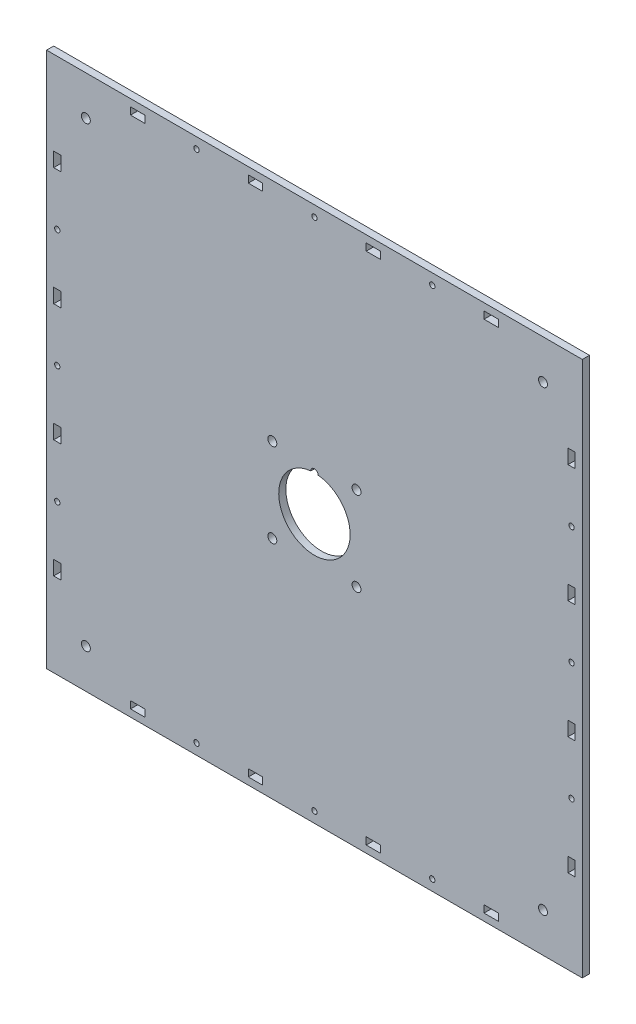
SolidWorks part; units mm, degrees
ref_plane "前视基准面" through (0, 0, 0) normal (0, 0, 1) x (1, 0, 0)
ref_plane "上视基准面" through (0, 0, 0) normal (0, 1, 0) x (1, 0, 0)
ref_plane "右视基准面" through (0, 0, 0) normal (1, 0, 0) x (0, 0, -1)
sketch "草图1" plane through (0, 0, 0) normal (0, 0, 1) x (1, 0, 0)
  line L0 (1.4571, -21.1871) -> (1.4571, -41.1871) construction
  line L2 (1.4571, -21.1871) -> (1.4571, 44.8129) construction
  line L4 (151.4571, -41.1871) -> (151.4571, 108.8129)
  line L5 (151.4571, 108.8129) -> (-148.5429, 108.8129)
  line L6 (-148.5429, 108.8129) -> (-148.5429, -191.1871)
  line L7 (-148.5429, -191.1871) -> (151.4571, -191.1871)
  line L8 (151.4571, -191.1871) -> (151.4571, -41.1871)
  line L9 (-148.5429, -41.1871) -> (-161.9412, -41.1871) construction
  line L10 (1.4571, -191.1871) -> (1.4571, -181.0361) construction
  circle A6 centre (1.4571, -21.1871) radius 241.4173 construction
  circle A9 centre (1.4571, -41.1871) radius 20
  circle A10 centre (25.0271, -17.6171) radius 2.5
  circle A11 centre (25.0271, -64.7571) radius 2.5
  circle A12 centre (-22.1129, -64.7571) radius 2.5
  circle A13 centre (-22.1129, -17.6171) radius 2.5
  dimension "D1" = 40
  dimension "D4" = 5
  dimension "D2" = 300
  dimension "D3" = 300
  dimension "D5" = 23.57
  dimension "D6" = 23.57
  dimension "D7" = 4
extrude "凸台-拉伸1" add sketch "草图1" along normal blind 4
sketch "草图2" plane through (0, 0, 4) normal (0, 0, 1) x (1, 0, 0)
  line L0 (-18.5429, -1.1871) -> (21.4571, -41.1871) construction
  circle A0 centre (1.4571, -21.1871) radius 2
extrude "切除-拉伸1" cut sketch "草图2" against normal blind 4 contours A0
sketch "草图3" plane through (0, 0, 4) normal (0, 0, 1) x (1, 0, 0)
  line L1 (96.4421, -183.1721) -> (104.4721, -183.1721)
  line L13 (1.4571, -191.1871) -> (1.4571, -185.1871) construction
  line L14 (-148.5429, -191.1871) -> (151.4571, -191.1871) construction
  line L15 (1.4571, -185.1871) -> (34.4571, -185.1871) construction
  line L16 (34.4571, -185.1871) -> (67.4571, -185.1871) construction
  line L17 (30.4421, -183.1721) -> (38.4721, -183.1721)
  line L18 (30.4421, -183.1721) -> (30.4421, -187.2021)
  line L19 (30.4421, -187.2021) -> (38.4721, -187.2021)
  line L20 (38.4721, -183.1721) -> (38.4721, -187.2021)
  line L21 (30.4421, -183.1721) -> (38.4721, -187.2021) construction
  line L22 (30.4421, -187.2021) -> (38.4721, -183.1721) construction
  line L23 (67.4571, -185.1871) -> (100.4571, -185.1871) construction
  line L24 (96.4421, -183.1721) -> (96.4421, -187.2021)
  line L25 (96.4421, -187.2021) -> (104.4721, -187.2021)
  line L26 (96.4421, -187.2021) -> (104.4721, -183.1721) construction
  line L27 (104.4721, -187.2021) -> (104.4721, -183.1721)
  line L28 (-35.5579, -183.1721) -> (-35.5579, -187.2021)
  line L29 (-27.5279, -183.1721) -> (-35.5579, -183.1721)
  line L30 (-27.5279, -183.1721) -> (-27.5279, -187.2021)
  line L31 (-27.5279, -187.2021) -> (-35.5579, -187.2021)
  line L32 (-93.5279, -183.1721) -> (-93.5279, -187.2021)
  line L33 (-101.5579, -187.2021) -> (-101.5579, -183.1721)
  line L34 (-93.5279, -183.1721) -> (-101.5579, -183.1721)
  line L35 (-93.5279, -187.2021) -> (-101.5579, -187.2021)
  line L36 (-140.5279, 53.7979) -> (-140.5279, 61.8279)
  line L37 (-144.5579, 53.7979) -> (-144.5579, 61.8279)
  line L38 (-144.5579, 61.8279) -> (-140.5279, 61.8279)
  line L39 (-140.5279, 53.7979) -> (-144.5579, 53.7979)
  line L40 (-140.5279, -12.2021) -> (-140.5279, -4.1721)
  line L41 (-140.5279, -4.1721) -> (-144.5579, -4.1721)
  line L42 (-144.5579, -12.2021) -> (-144.5579, -4.1721)
  line L43 (-140.5279, -12.2021) -> (-144.5579, -12.2021)
  line L44 (-140.5279, -70.1721) -> (-144.5579, -70.1721)
  line L45 (-140.5279, -70.1721) -> (-140.5279, -78.2021)
  line L46 (-144.5579, -70.1721) -> (-144.5579, -78.2021)
  line L47 (-140.5279, -78.2021) -> (-144.5579, -78.2021)
  line L48 (-140.5279, -136.1721) -> (-140.5279, -144.2021)
  line L49 (-144.5579, -136.1721) -> (-144.5579, -144.2021)
  line L50 (-140.5279, -136.1721) -> (-144.5579, -136.1721)
  line L51 (-144.5579, -144.2021) -> (-140.5279, -144.2021)
  line L52 (96.4421, 100.7979) -> (104.4721, 100.7979)
  line L53 (96.4421, 104.8279) -> (104.4721, 104.8279)
  line L54 (104.4721, 104.8279) -> (104.4721, 100.7979)
  line L55 (96.4421, 100.7979) -> (96.4421, 104.8279)
  line L56 (30.4421, 100.7979) -> (38.4721, 100.7979)
  line L57 (38.4721, 100.7979) -> (38.4721, 104.8279)
  line L58 (30.4421, 104.8279) -> (38.4721, 104.8279)
  line L59 (30.4421, 100.7979) -> (30.4421, 104.8279)
  line L60 (-27.5279, 100.7979) -> (-27.5279, 104.8279)
  line L61 (-27.5279, 100.7979) -> (-35.5579, 100.7979)
  line L62 (-27.5279, 104.8279) -> (-35.5579, 104.8279)
  line L63 (-35.5579, 100.7979) -> (-35.5579, 104.8279)
  line L64 (-93.5279, 100.7979) -> (-101.5579, 100.7979)
  line L65 (-93.5279, 104.8279) -> (-101.5579, 104.8279)
  line L66 (-93.5279, 100.7979) -> (-93.5279, 104.8279)
  line L67 (-101.5579, 104.8279) -> (-101.5579, 100.7979)
  line L68 (143.4421, -136.1721) -> (143.4421, -144.2021)
  line L69 (147.4721, -136.1721) -> (147.4721, -144.2021)
  line L70 (147.4721, -144.2021) -> (143.4421, -144.2021)
  line L71 (143.4421, -136.1721) -> (147.4721, -136.1721)
  line L72 (143.4421, -70.1721) -> (143.4421, -78.2021)
  line L73 (143.4421, -78.2021) -> (147.4721, -78.2021)
  line L74 (147.4721, -70.1721) -> (147.4721, -78.2021)
  line L75 (143.4421, -70.1721) -> (147.4721, -70.1721)
  line L76 (143.4421, -12.2021) -> (147.4721, -12.2021)
  line L77 (143.4421, -12.2021) -> (143.4421, -4.1721)
  line L78 (147.4721, -12.2021) -> (147.4721, -4.1721)
  line L79 (143.4421, -4.1721) -> (147.4721, -4.1721)
  line L80 (143.4421, 53.7979) -> (143.4421, 61.8279)
  line L81 (147.4721, 53.7979) -> (147.4721, 61.8279)
  line L82 (143.4421, 53.7979) -> (147.4721, 53.7979)
  line L83 (147.4721, 61.8279) -> (143.4421, 61.8279)
  circle A0 centre (1.4571, -185.1871) radius 1.5
  circle A1 centre (67.4571, -185.1871) radius 1.5
  circle A2 centre (-64.5429, -185.1871) radius 1.5
  circle A3 centre (-142.5429, 24.8129) radius 1.5
  circle A4 centre (-142.5429, -41.1871) radius 1.5
  circle A5 centre (-142.5429, -107.1871) radius 1.5
  circle A6 centre (67.4571, 102.8129) radius 1.5
  circle A7 centre (1.4571, 102.8129) radius 1.5
  circle A8 centre (-64.5429, 102.8129) radius 1.5
  circle A9 centre (145.4571, -107.1871) radius 1.5
  circle A10 centre (145.4571, -41.1871) radius 1.5
  circle A11 centre (145.4571, 24.8129) radius 1.5
  dimension "D1" = 8.03
  dimension "D3" = 4
  dimension "D2" = 4.03
extrude "切除-拉伸2" cut sketch "草图3" against normal blind 4
sketch "草图4" plane through (0, 0, 4) normal (0, 0, 1) x (1, 0, 0)
  line L2 (1.4571, 102.8129) -> (-142.5429, 102.8129) construction
  line L3 (-142.5429, 102.8129) -> (-38.5429, -1.1871) construction
  line L4 (1.4571, -1.1871) -> (-38.5429, -1.1871) construction
  line L5 (1.4571, 102.8129) -> (1.4571, -1.1871) construction
  line L6 (-9.5429, 88.8129) -> (-9.5429, 12.8129)
  line L7 (-12.5429, 9.8129) -> (-32.7439, 9.8129)
  line L8 (-110.8652, 86.6915) -> (-34.8652, 10.6915)
  line L9 (-12.5429, 91.8129) -> (-108.7439, 91.8129)
  line L10 (-9.5429, 91.8129) -> (-115.9865, 91.8129) construction
  line L11 (-115.9865, 91.8129) -> (-33.9865, 9.8129) construction
  line L12 (-9.5429, 91.8129) -> (-9.5429, 9.8129) construction
  line L13 (-9.5429, 9.8129) -> (-33.9865, 9.8129) construction
  line L14 (12.4571, 88.8129) -> (12.4571, 12.8129)
  line L15 (15.4571, 9.8129) -> (35.6582, 9.8129)
  line L16 (113.7795, 86.6915) -> (37.7795, 10.6915)
  line L17 (15.4571, 91.8129) -> (111.6582, 91.8129)
  line L18 (1.4571, -41.1871) -> (42.8173, -41.1871) construction
  line L19 (-12.5429, -174.1871) -> (-108.7439, -174.1871)
  line L20 (-110.8652, -169.0658) -> (-34.8652, -93.0658)
  line L21 (-12.5429, -92.1871) -> (-32.7439, -92.1871)
  line L22 (-9.5429, -171.1871) -> (-9.5429, -95.1871)
  line L23 (-49.5429, -27.1871) -> (-49.5429, -6.9861)
  line L24 (15.4571, -174.1871) -> (111.6582, -174.1871)
  line L25 (113.7795, -169.0658) -> (37.7795, -93.0658)
  line L26 (15.4571, -92.1871) -> (35.6582, -92.1871)
  line L27 (12.4571, -171.1871) -> (12.4571, -95.1871)
  line L28 (-128.5429, -30.1871) -> (-52.5429, -30.1871)
  line L29 (-131.5429, -27.1871) -> (-131.5429, 69.0139)
  line L30 (-126.4215, 71.1352) -> (-50.4215, -4.8648)
  line L31 (129.3358, 71.1352) -> (53.3358, -4.8648)
  line L32 (134.4571, -27.1871) -> (134.4571, 69.0139)
  line L33 (131.4571, -30.1871) -> (55.4571, -30.1871)
  line L34 (52.4571, -27.1871) -> (52.4571, -6.9861)
  line L35 (52.4571, -55.1871) -> (52.4571, -75.3882)
  line L36 (131.4571, -52.1871) -> (55.4571, -52.1871)
  line L37 (134.4571, -55.1871) -> (134.4571, -151.3882)
  line L38 (129.3358, -153.5095) -> (53.3358, -77.5095)
  line L39 (-126.4215, -153.5095) -> (-50.4215, -77.5095)
  line L40 (-131.5429, -55.1871) -> (-131.5429, -151.3882)
  line L41 (-128.5429, -52.1871) -> (-52.5429, -52.1871)
  line L42 (-49.5429, -55.1871) -> (-49.5429, -75.3882)
  arc A0 (-108.7439, 91.8129) -> (-110.8652, 86.6915) centre (-108.7439, 88.8129) ccw
  arc A1 (-9.5429, 12.8129) -> (-12.5429, 9.8129) centre (-12.5429, 12.8129) cw
  arc A2 (-32.7439, 9.8129) -> (-34.8652, 10.6915) centre (-32.7439, 12.8129) cw
  arc A3 (-9.5429, 88.8129) -> (-12.5429, 91.8129) centre (-12.5429, 88.8129) ccw
  arc A4 (111.6582, 91.8129) -> (113.7795, 86.6915) centre (111.6582, 88.8129) cw
  arc A5 (12.4571, 88.8129) -> (15.4571, 91.8129) centre (15.4571, 88.8129) cw
  arc A6 (12.4571, 12.8129) -> (15.4571, 9.8129) centre (15.4571, 12.8129) ccw
  arc A7 (35.6582, 9.8129) -> (37.7795, 10.6915) centre (35.6582, 12.8129) ccw
  arc A8 (-9.5429, -171.1871) -> (-12.5429, -174.1871) centre (-12.5429, -171.1871) cw
  arc A9 (-32.7439, -92.1871) -> (-34.8652, -93.0658) centre (-32.7439, -95.1871) ccw
  arc A10 (-9.5429, -95.1871) -> (-12.5429, -92.1871) centre (-12.5429, -95.1871) ccw
  arc A11 (-108.7439, -174.1871) -> (-110.8652, -169.0658) centre (-108.7439, -171.1871) cw
  arc A12 (35.6582, -92.1871) -> (37.7795, -93.0658) centre (35.6582, -95.1871) cw
  arc A13 (12.4571, -95.1871) -> (15.4571, -92.1871) centre (15.4571, -95.1871) cw
  arc A14 (12.4571, -171.1871) -> (15.4571, -174.1871) centre (15.4571, -171.1871) ccw
  arc A15 (111.6582, -174.1871) -> (113.7795, -169.0658) centre (111.6582, -171.1871) ccw
  arc A16 (-128.5429, -30.1871) -> (-131.5429, -27.1871) centre (-128.5429, -27.1871) cw
  arc A17 (-131.5429, 69.0139) -> (-126.4215, 71.1352) centre (-128.5429, 69.0139) cw
  arc A18 (-49.5429, -6.9861) -> (-50.4215, -4.8648) centre (-52.5429, -6.9861) ccw
  arc A19 (-52.5429, -30.1871) -> (-49.5429, -27.1871) centre (-52.5429, -27.1871) ccw
  arc A20 (55.4571, -30.1871) -> (52.4571, -27.1871) centre (55.4571, -27.1871) cw
  arc A21 (52.4571, -6.9861) -> (53.3358, -4.8648) centre (55.4571, -6.9861) cw
  arc A22 (134.4571, 69.0139) -> (129.3358, 71.1352) centre (131.4571, 69.0139) ccw
  arc A23 (131.4571, -30.1871) -> (134.4571, -27.1871) centre (131.4571, -27.1871) ccw
  arc A24 (131.4571, -52.1871) -> (134.4571, -55.1871) centre (131.4571, -55.1871) cw
  arc A25 (134.4571, -151.3882) -> (129.3358, -153.5095) centre (131.4571, -151.3882) cw
  arc A26 (52.4571, -75.3882) -> (53.3358, -77.5095) centre (55.4571, -75.3882) ccw
  arc A27 (55.4571, -52.1871) -> (52.4571, -55.1871) centre (55.4571, -55.1871) ccw
  arc A28 (-52.5429, -52.1871) -> (-49.5429, -55.1871) centre (-52.5429, -55.1871) cw
  arc A29 (-49.5429, -75.3882) -> (-50.4215, -77.5095) centre (-52.5429, -75.3882) cw
  arc A30 (-131.5429, -151.3882) -> (-126.4215, -153.5095) centre (-128.5429, -151.3882) ccw
  arc A31 (-128.5429, -52.1871) -> (-131.5429, -55.1871) centre (-128.5429, -55.1871) ccw
  dimension "D2" = 3
  dimension "D3" = 3
  dimension "D1" = 11
sketch "草图5" plane through (0, 0, 4) normal (0, 0, 1) x (1, 0, 0)
  line L0 (1.4571, -41.1871) -> (-148.5429, 108.8129) construction
  line L1 (-126.5429, 86.8129) -> (-126.5429, 108.8129) construction
  line L2 (151.4571, 108.8129) -> (-148.5429, 108.8129) construction
  circle A0 centre (-126.5429, 86.8129) radius 2.5
  circle A1 centre (129.4571, 86.8129) radius 2.5
  circle A2 centre (129.4571, -169.1871) radius 2.5
  circle A3 centre (-126.5429, -169.1871) radius 2.5
  dimension "D1" = 4
extrude "切除-拉伸4" cut sketch "草图5" against normal blind 10
